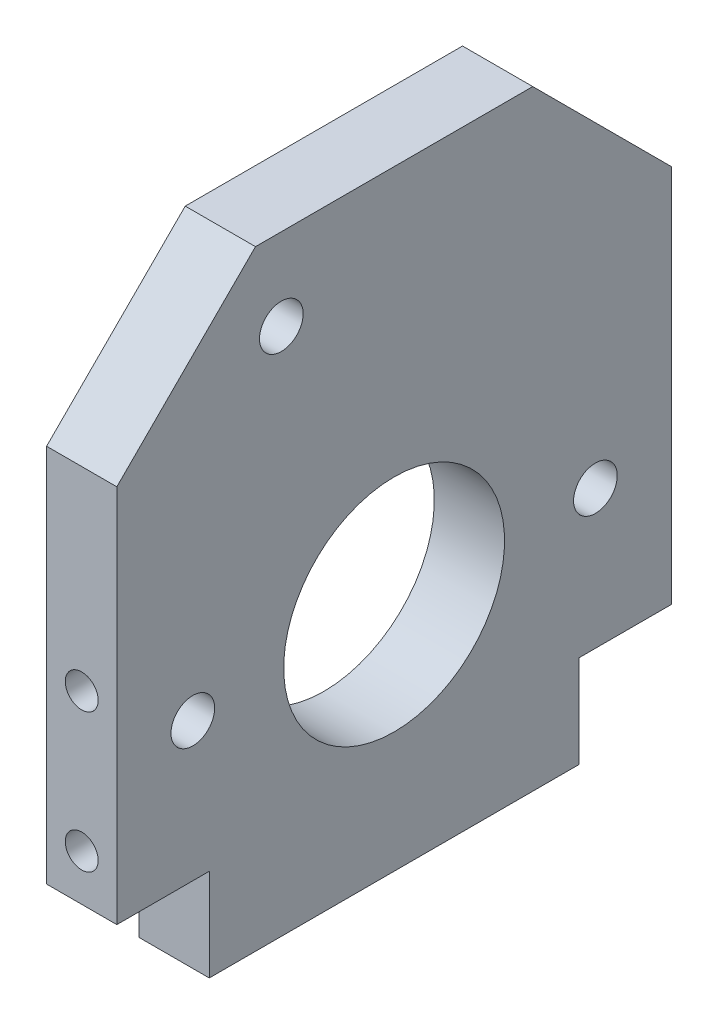
SolidWorks part; units mm, degrees
material "1060 Alloy"
ref_plane "Front" through (0, 0, 0) normal (0, 0, 1) x (1, 0, 0)
ref_plane "Top" through (0, 0, 0) normal (0, 1, 0) x (1, 0, 0)
ref_plane "Right" through (0, 0, 0) normal (1, 0, 0) x (0, 0, -1)
sketch "Sketch1" plane through (0, 0, 0) normal (1, 0, 0) x (0, 0, -1)
  line L0 (16.9529, -11.6427) -> (-8.4471, -11.6427) construction
  line L1 (-14.7971, 30.2823) -> (23.3029, 30.2823)
  line L2 (-14.7971, 30.2823) -> (-14.7971, -5.2927)
  line L3 (-8.4471, -11.6427) -> (16.9529, -11.6427)
  line L4 (23.3029, 30.2823) -> (23.3029, -5.2927)
  line L8 (-14.7971, -5.2927) -> (-8.4471, -5.2927)
  line L9 (-8.4471, -11.6427) -> (-8.4471, -5.2927)
  line L12 (23.3029, -5.2927) -> (16.9529, -5.2927)
  line L13 (16.9529, -11.6427) -> (16.9529, -5.2927)
  circle A1 centre (4.2529, 11.2323) radius 18.5 construction
  circle A5 centre (4.2529, 4.2323) radius 7.5875
  circle A6 centre (4.2529, 4.2323) radius 7.5875
  dimension "D1" = 19.05
  dimension "D2" = 19.05
  dimension "D3" = 19.05
  dimension "D4" = 25.4
  dimension "D6" = 6.35
  dimension "D5" = 1.5875
extrude "Boss-Extrude1" add sketch "Sketch1" along normal blind 4.826
hole_wizard "Ø3.0 (3) Diameter Hole1" positions "Sketch2" profile "Sketch3" hole size "Ø3.0" standard "ANSI Metric" end condition through all
sketch "Sketch2" plane through (0, 0, 0) normal (-1, 0, 0) x (0, 0, 1)
  point P0 (3.4971, 24.6557)
  point P3 (9.5764, 4.2323)
  point P6 (-18.0822, 4.2323)
sketch "Sketch3" plane through (0, 24.6557, 3.4971) normal (0, 1, 0) x (0, 0, 1)
  line L0 (0, 0) -> (0, 4.826)
  line L1 (0, 4.826) -> (1.5, 4.826)
  line L2 (1.5, 4.826) -> (1.5, 0)
  line L5 (1.5, 0) -> (0, 0)
  line L11 (0, -6.35) -> (0, 107.95) construction
  dimension "Thru Hole Dia." = 3
  dimension "Thru Hole Depth" = 4.826
chamfer "Chamfer1" distance 9.525 angle 45 2 edges at (2.413, 30.2823, -23.3029) (2.413, 30.2823, 14.7971)
hole_wizard "#4-40 Tapped Hole1" positions "Sketch4" profile "Sketch5" tap size "#4-40" standard "ANSI Inch"
sketch "Sketch4" plane through (-40.9593, -24.0447, -23.3029) normal (0, 0, -1) x (-1, 0, 0)
  point P0 (-43.3723, 31.452)
  point P1 (-43.3723, 21.927)
sketch "Sketch5" plane through (2.413, 7.4073, -23.3029) normal (1, 0, 0) x (0, 1, 0)
  line L0 (0, 0) -> (0, 8.2992)
  line L1 (0, 8.2992) -> (1.1303, 7.62)
  line L2 (1.1303, 7.62) -> (1.1303, 0)
  line L5 (1.1303, 0) -> (0, 0)
  line L10 (0, 8.2992) -> (-1.1303, 7.62) construction
  line L11 (0, -6.35) -> (0, 107.95) construction
  dimension "Tap Drill Dia." = 2.2606
  dimension "Tap Drill Depth" = 7.62
  dimension "Drill Angle" = 118
cosmetic thread "Hole Thread1" parameters "D1"=5.588, "D2"=2.8448
cosmetic thread "Hole Thread2" parameters "D1"=5.588, "D2"=2.8448
hole_wizard "#4-40 Tapped Hole2" positions "Sketch6" profile "Sketch7" tap size "#4-40" standard "ANSI Inch"
sketch "Sketch6" plane through (-40.9593, -24.0447, 14.7971) normal (0, 0, 1) x (1, 0, 0)
  point P0 (43.3723, 21.927)
  point P1 (43.3723, 31.452)
cosmetic thread "Hole Thread3" parameters "D1"=5.588, "D2"=2.8448
cosmetic thread "Hole Thread4" parameters "D1"=5.588, "D2"=2.8448
sketch "Sketch7" plane through (2.413, -2.1177, 14.7971) normal (1, 0, 0) x (0, -1, 0)
  line L0 (0, 0) -> (0, 8.2992)
  line L1 (0, 8.2992) -> (1.1303, 7.62)
  line L2 (1.1303, 7.62) -> (1.1303, 0)
  line L5 (1.1303, 0) -> (0, 0)
  line L10 (0, 8.2992) -> (-1.1303, 7.62) construction
  line L11 (0, -6.35) -> (0, 107.95) construction
  dimension "Tap Drill Dia." = 2.2606
  dimension "Tap Drill Depth" = 7.62
  dimension "Drill Angle" = 118
